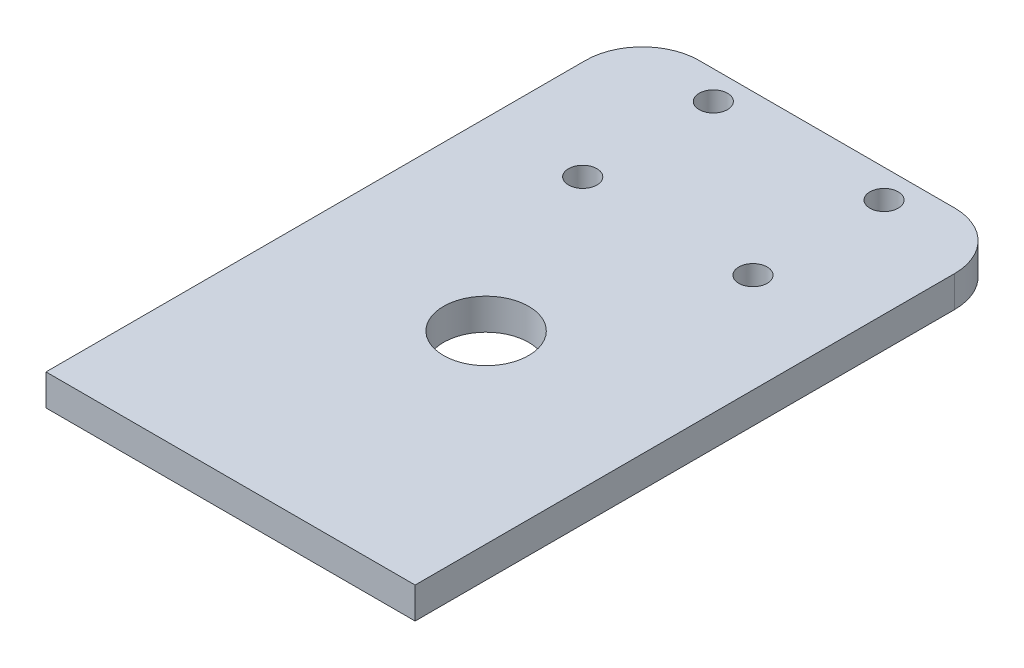
SolidWorks part; units mm, degrees
ref_plane "Alzado" through (0, 0, 0) normal (0, 0, 1) x (1, 0, 0)
ref_plane "Planta" through (0, 0, 0) normal (0, 1, 0) x (1, 0, 0)
ref_plane "Vista lateral" through (0, 0, 0) normal (1, 0, 0) x (0, 0, -1)
sketch "Croquis1" plane through (0, 0, 0) normal (0, 1, 0) x (1, 0, 0)
  line L0 (-100.4158, 6.0772) -> (-35.4158, 6.0772)
  line L1 (-82.9065, 1.0772) -> (-82.9065, -21.9228) construction
  line L2 (-82.9065, 1.0772) -> (-82.9065, 6.0772) construction
  line L3 (-67.9158, 6.0772) -> (-67.9158, -53.9228) construction
  line L4 (-100.4158, 6.0772) -> (-100.4158, -98.9228)
  line L5 (-100.4158, -98.9228) -> (-35.4158, -98.9228)
  line L6 (-35.4158, -98.9228) -> (-35.4158, 6.0772)
  line L7 (-52.8399, 1.0772) -> (-52.925, -21.9228) construction
  circle A0 centre (-82.9065, 1.0772) radius 2.5
  circle A1 centre (-52.8399, 1.0772) radius 2.5
  circle A2 centre (-82.9065, -21.9228) radius 2.5
  circle A3 centre (-52.925, -21.9228) radius 2.5
  circle A4 centre (-67.9158, -53.9228) radius 7.5
  dimension "D4" = 5
  dimension "D5" = 5
  dimension "D6" = 5
  dimension "D10" = 15
  dimension "D1" = 65
  dimension "D2" = 5
  dimension "D3" = 23
  dimension "D7" = 105
  dimension "D8" = 23
  dimension "D9" = 60
extrude "Saliente-Extruir1" add sketch "Croquis1" along normal blind 5.5
fillet "Redondeo1" radius 10 1 edges at (-35.4158, 2.75, -6.0772)
fillet "Redondeo2" radius 10 1 edges at (-100.4158, 2.75, -6.0772)
